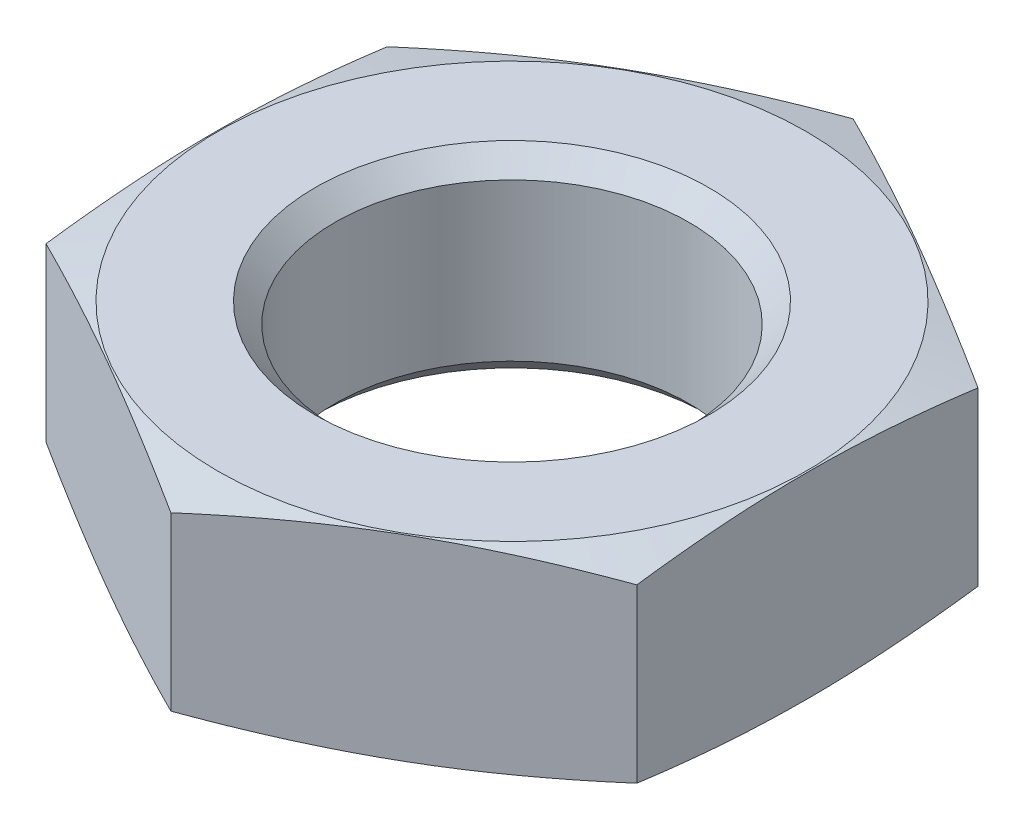
SolidWorks part; units mm, degrees
ref_plane "Ebene vorne" through (0, 0, 0) normal (0, 0, 1) x (1, 0, 0)
ref_plane "Ebene oben" through (0, 0, 0) normal (0, 1, 0) x (1, 0, 0)
ref_plane "Ebene rechts" through (0, 0, 0) normal (1, 0, 0) x (0, 0, -1)
sketch "Skizze1" plane through (0, 0, 0) normal (0, 0, 1) x (1, 0, 0)
  line L0 (0, 0) -> (11.95, 0)
  line L1 (11.95, 0) -> (26.8782, -4)
  line L2 (26.8782, -4) -> (11.95, -8)
  line L3 (11.95, -8) -> (0, -8)
  line L4 (0, -8) -> (0, 0)
  line L5 (0, -8) -> (0, 0) construction
revolve "Rotation1" add sketch "Skizze1" angle 360 about L5
sketch "Skizze2" plane through (0, 0, 0) normal (0, 1, 0) x (1, 0, 0)
  line L0 (-48, 48) -> (-48, -48)
  line L1 (-48, -48) -> (48, -48)
  line L2 (48, -48) -> (48, 48)
  line L3 (48, 48) -> (-48, 48)
  line L4 (-12, -6.9282) -> (0, -13.8564)
  line L5 (0, -13.8564) -> (12, -6.9282)
  line L6 (12, -6.9282) -> (12, 6.9282)
  line L7 (12, 6.9282) -> (0, 13.8564)
  line L8 (0, 13.8564) -> (-12, 6.9282)
  line L9 (-12, 6.9282) -> (-12, -6.9282)
extrude "Schnitt-Linear austragen1" cut sketch "Skizze2" along normal blind 9 and the other way blind 9
sketch "Skizze3" plane through (0, 0, 0) normal (0, 0, 1) x (1, 0, 0)
  line L0 (0, 0) -> (8, 0)
  line L1 (8, 0) -> (7.188, -0.812)
  line L2 (7.188, -0.812) -> (7.188, -7.188)
  line L3 (7.188, -7.188) -> (8, -8)
  line L4 (8, -8) -> (0, -8)
  line L5 (0, -8) -> (0, 0)
  line L6 (0, -8) -> (0, 0) construction
revolve "Schnitt-Rotation1" cut sketch "Skizze3" angle 360 about L6 reverse direction yes
cosmetic thread "Gewindedarstellung1" parameters "D1"=8, "D2"=16
ref_plane "Ebene1" through (0, -4, 0) normal (0, 1, 0) x (1, 0, 0)
ref_plane "2CYL XY" through (0, -4, 0) normal (0, 1, 0) x (1, 0, 0)
ref_plane "2CYL XZ" through (0, 0, 0) normal (0, 0, 1) x (1, 0, 0)
ref_plane "2CYL YZ" through (0, 0, 0) normal (1, 0, 0) x (0, 0, -1)
ref_axis "2CYL X" through (-80.9, -4, 0) along (1, 0, 0)
ref_axis "2CYL Y" through (0, -4, 50) along (0, 0, -1)
ref_axis "2CYL Z" through (0, 50, 0) along (0, -1, 0)
sketch3d "2CYL"
  point P0 (0, -4, 0)
ref_plane "din439b_punkt XY" through (0, 0, 0) normal (0, 1, 0) x (1, 0, 0)
ref_plane "din439b_punkt XZ" through (0, 0, 0) normal (0, 0, 1) x (1, 0, 0)
ref_plane "din439b_punkt YZ" through (0, 0, 0) normal (1, 0, 0) x (0, 0, -1)
ref_axis "din439b_punkt X" through (-80.9, 0, 0) along (1, 0, 0)
ref_axis "din439b_punkt Y" through (0, 0, 50) along (0, 0, -1)
ref_axis "din439b_punkt Z" through (0, 50, 0) along (0, -1, 0)
sketch3d "din439b_punkt"
  point P0 (0, 0, 0)
